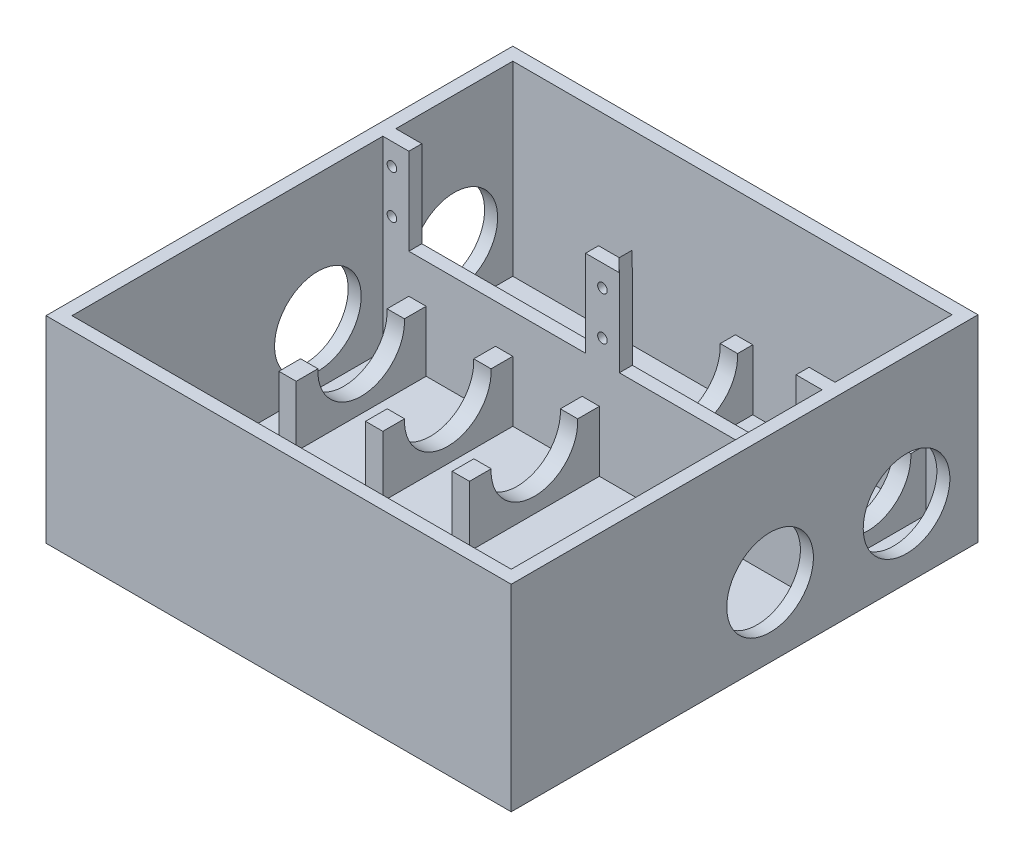
SolidWorks part; units mm, degrees
ref_plane "Front Plane" through (0, 0, 0) normal (0, 0, 1) x (1, 0, 0)
ref_plane "Top Plane" through (0, 0, 0) normal (0, 1, 0) x (1, 0, 0)
ref_plane "Right Plane" through (0, 0, 0) normal (1, 0, 0) x (0, 0, -1)
sketch "Sketch3" plane through (0, 0, 0) normal (0, 1, 0) x (1, 0, 0)
  line L1 (0, 0) -> (-107.4, 0)
  line L2 (0, 0) -> (0, -136.7612)
  line L3 (0, -136.7612) -> (-107.4, -136.7612)
  line L4 (-107.4, 0) -> (-107.4, -136.7612)
  dimension "D1" = 107.4
extrude "Boss-Extrude2" add sketch "Sketch3" along normal blind 2.5
sketch "Sketch4" plane through (0, 2.5, 0) normal (0, 1, 0) x (1, 0, 0)
  line L0 (-107.4, 0) -> (-107.4, -136.7612) construction
  line L1 (0, 0) -> (-107.4, 0) construction
  line L2 (-29, 0) -> (-29, -30)
  line L3 (-53, 0) -> (-49, 0)
  line L4 (-53, 0) -> (-53, -30)
  line L5 (-53, -30) -> (-49, -30)
  line L6 (-49, 0) -> (-49, -30)
  line L7 (-33, 0) -> (-33, -30)
  line L8 (-33, 0) -> (-29, 0)
  line L9 (-33, -30) -> (-29, -30)
  line L10 (-9, 0) -> (-9, -30)
  line L11 (-13, 0) -> (-13, -30)
  line L12 (-13, 0) -> (-9, 0)
  line L13 (-13, -30) -> (-9, -30)
  line L14 (-74.4, -33) -> (-74.4, -63)
  line L15 (-98.4, -33) -> (-94.4, -33)
  line L16 (-98.4, -33) -> (-98.4, -63)
  line L17 (-98.4, -63) -> (-94.4, -63)
  line L18 (-94.4, -33) -> (-94.4, -63)
  line L19 (-78.4, -33) -> (-78.4, -63)
  line L20 (-78.4, -33) -> (-74.4, -33)
  line L21 (-78.4, -63) -> (-74.4, -63)
  line L22 (-54.4, -33) -> (-54.4, -63)
  line L23 (-58.4, -33) -> (-58.4, -63)
  line L24 (-58.4, -33) -> (-54.4, -33)
  line L25 (-58.4, -63) -> (-54.4, -63)
  line L26 (0, -136.7612) -> (0, 0) construction
  point P0 (-100.4, -3)
  point P1 (-20.4, -3)
  point P7 (-100.4, -23)
  point P8 (-20.4, -23)
  dimension "D1" = 80
  dimension "D2" = 7
  dimension "D3" = 3
  dimension "D4" = 3
  dimension "D6" = 30
  dimension "D7" = 4
  dimension "D8" = 9
  dimension "D10" = 16
  dimension "D11" = 16
  dimension "D12" = 9
  dimension "D13" = 9
  dimension "D14" = 16
  dimension "D15" = 16
  dimension "D16" = 3
  dimension "D5" = 2
  dimension "D9" = 2
extrude "Boss-Extrude3" add sketch "Sketch4" along normal blind 14
sketch "Sketch7" plane through (0, 2.5, 0) normal (0, 1, 0) x (1, 0, 0)
  line L69 (-3, -3) -> (-9, -3)
  line L70 (-3, -133.7612) -> (-3, -3)
  line L71 (-104.4, -133.7612) -> (-3, -133.7612)
  line L72 (-53, -3) -> (-104.4, -3)
  line L73 (-104.4, -3) -> (-104.4, -133.7612)
  line L74 (-3, -3) -> (-9, -3)
  line L75 (-3, -133.7612) -> (-3, -3)
  line L76 (-104.4, -133.7612) -> (-3, -133.7612)
  line L77 (-53, -3) -> (-104.4, -3)
  line L78 (-104.4, -3) -> (-104.4, -133.7612)
  line L85 (-13, -3) -> (-29, -3)
  line L86 (-13, -3) -> (-29, -3)
  line L87 (-33, -3) -> (-33, 0)
  line L88 (-33, -3) -> (-49, -3)
  line L89 (-33, -3) -> (-49, -3)
  line L90 (-33, 0) -> (-49, 0)
  line L91 (-13, -3) -> (-13, 0)
  line L92 (-13, 0) -> (-29, 0)
  line L93 (-29, 0) -> (-29, -3)
  line L94 (-49, 0) -> (-49, -3)
  line L115 (-53, 0) -> (-107.4, 0)
  line L116 (-107.4, 0) -> (-107.4, -136.7612)
  line L117 (-107.4, -136.7612) -> (0, -136.7612)
  line L118 (0, 0) -> (-9, 0)
  line L119 (0, -136.7612) -> (0, 0)
  line L120 (-53, 0) -> (-107.4, 0)
  line L121 (-107.4, 0) -> (-107.4, -136.7612)
  line L122 (-107.4, -136.7612) -> (0, -136.7612)
  line L123 (0, 0) -> (-9, 0)
  line L124 (0, -136.7612) -> (0, 0)
  line M21 (-13, -30) -> (-13, 0)
  line M22 (-13, 0) -> (-29, 0)
  line M23 (-29, 0) -> (-29, -30)
  line M25 (-33, -30) -> (-33, 0)
  line M26 (-33, 0) -> (-49, 0)
  line M27 (-49, 0) -> (-49, -30)
  line M29 (-53, -30) -> (-53, 0)
  line M30 (-53, 0) -> (-107.4, 0)
  line M31 (-107.4, 0) -> (-107.4, -136.7612)
  line M32 (-107.4, -136.7612) -> (0, -136.7612)
  line M33 (0, -136.7612) -> (0, 0)
  line M34 (0, 0) -> (-9, 0)
  line M35 (-9, 0) -> (-9, -30)
  dimension "D1" = 3
  dimension "D2" = 3
  dimension "D3" = 3
  dimension "D5" = 0
extrude "Boss-Extrude5" add sketch "Sketch7" along normal blind 26 contours L89 M25 M26 M27 | L78 L77 L74 L75 L76 M29 M30 M31 M32 M33 M34 M35 | L86 M21 M22 M23 region at (-6, 2.5, 1.2611) region at (-21, 2.5, 1.5) region at (-41, 2.5, 1.5)
sketch "Sketch8" plane through (0, 2.5, 0) normal (0, 1, 0) x (1, 0, 0)
  line L0 (-104.4, -3) -> (-104.4, -133.7612) construction
  circle A0 centre (-72.4, -69) radius 1
  circle A1 centre (-26.68, -69) radius 1
  circle A2 centre (-26.68, -84.24) radius 1
  circle A3 centre (-72.4, -84.24) radius 1
  point P0 (-72.4, -69)
  point P2 (-26.68, -69)
  point P7 (-26.68, -84.24)
  point P8 (-72.4, -84.24)
  dimension "D4" = 2
  dimension "D1" = 32
  dimension "D2" = 6
  dimension "D5" = 2
  dimension "D3" = 2
  dimension "D6" = 2
extrude "Cut-Extrude3" cut sketch "Sketch8" against normal through all
sketch "Sketch10" plane through (0, 2.5, 0) normal (0, 1, 0) x (1, 0, 0)
  line L0 (-3, -133.7612) -> (-3, -3) construction
  line L1 (-3, -30) -> (-104.4, -30)
  line L2 (-3, -30) -> (-3, -33)
  line L3 (-3, -33) -> (-104.4, -33)
  line L4 (-104.4, -30) -> (-104.4, -33)
  line L5 (-104.4, -3) -> (-104.4, -133.7612) construction
  point P16 (-3, -77)
  point P19 (-104.4, -77)
  dimension "D1" = 3
  dimension "D2" = 0
extrude "Boss-Extrude6" add sketch "Sketch10" along normal blind 46
sketch "Sketch14" plane through (0, 0, 0) normal (0, -1, 0) x (1, 0, 0)
  line L1 (-107.4, 0) -> (-107.4, 136.7612) construction
  line L2 (0, 136.7612) -> (-107.4, 136.7612)
  line L3 (0, 136.7612) -> (0, 107.7612)
  line L4 (0, 107.7612) -> (-107.4, 107.7612)
  line L5 (-107.4, 136.7612) -> (-107.4, 107.7612)
  dimension "D1" = 29
extrude "Cut-Extrude7" cut sketch "Sketch14" against normal through all
sketch "Sketch15" plane through (0, 0, 33) normal (0, 0, 1) x (1, 0, 0)
  line L0 (-98.4, 48.5) -> (-98.4, 25.5)
  line L1 (-98.4, 25.5) -> (-57.6, 25.5)
  line L2 (-57.6, 48.5) -> (-57.6, 25.5)
  line L3 (-104.4, 48.5) -> (-3, 48.5) construction
  line L4 (-49.8234, 48.6106) -> (-49.8, 25.5)
  line L5 (-49.8, 25.5) -> (-9, 25.5)
  line L6 (-9, 48.5) -> (-9, 25.5)
  line L7 (-9, 48.5) -> (-49.8, 48.5)
  line L8 (-49.8, 48.5) -> (-49.8234, 48.6106)
  line L9 (-49.8, 48.5) -> (-49.8, 25.5) [skipped]
  circle A0 centre (-102.3, 30.5) radius 1.1036
  circle A3 centre (-102.3, 40.5) radius 1.1036
  circle A4 centre (-53.7, 30.5) radius 1.1036
  circle A5 centre (-53.7, 40.5) radius 1.1036
  circle A6 centre (-5.1, 40.5) radius 1.1036
  circle A7 centre (-5.1, 30.5) radius 1.1036
  point P6 (-78, 25.5)
  line M6 (-3, 48.5) -> (-104.4, 48.5)
  dimension "D13" = 0
  dimension "D1" = 24.3
  dimension "D4" = 0
  dimension "D5" = 6
  dimension "D6" = 8
  dimension "D7" = 40.8
  dimension "D9" = 23
  dimension "D11" = 10
  dimension "D14" = 2
extrude "Cut-Extrude11" cut sketch "Sketch15" against normal blind 14 contours L6 L4 L5 M6 | L2 L0 L1 M6 | A5 | A4 | A3 | A6 | A7 | A4 | A0 region at (-78, 37, 33) region at (-49.8078, 40.8333, 33) region at (-29.4, 37, 33) region at (-102.3, 40.5, 33) region at (-53.7, 30.5, 33) region at (-53.7, 40.5, 33) region at (-5.1, 40.5, 33) region at (-5.1, 30.5, 33)
sketch "Sketch17" plane through (-107.4, 0, 0) normal (-1, 0, 0) x (0, 0, 1)
  line L0 (0, 28.5) -> (0, 0) construction
  line L1 (0, 0) -> (107.7612, 0) construction
  circle A0 centre (16.5, 16) radius 10
  circle A1 centre (48, 16) radius 10
  point P0 (16.5, 16)
  point P3 (0, 14.25)
  point P8 (48, 16)
  dimension "D3" = 20
  dimension "D5" = 20
  dimension "D1" = 16.5
  dimension "D2" = 16
  dimension "D4" = 48
extrude "Cut-Extrude12" cut sketch "Sketch17" against normal through all
sketch "Sketch18" plane through (0, 2.5, 0) normal (0, 1, 0) x (1, 0, 0)
  line L0 (-104.4, -33) -> (-104.4, -107.7612) construction
  line L1 (-3, -107.7612) -> (-104.4, -107.7612)
  line L2 (-3, -107.7612) -> (-3, -104.7612)
  line L3 (-3, -104.7612) -> (-104.4, -104.7612)
  line L4 (-104.4, -107.7612) -> (-104.4, -104.7612)
  dimension "D1" = 3
extrude "Boss-Extrude7" add sketch "Sketch18" along normal blind 26
sketch "Sketch19" plane through (0, 16.5, 0) normal (0, 1, 0) x (1, 0, 0)
  line L0 (-33, -3) -> (-33, -6.5125) construction
  line L1 (-49, 0) -> (-53, 0)
  line L2 (-49, 0) -> (-49, -3)
  line L3 (-49, -3) -> (-53, -3)
  line L4 (-53, 0) -> (-53, -3)
  line L5 (-29, 0) -> (-33, 0)
  line L6 (-29, 0) -> (-29, -3)
  line L7 (-29, -3) -> (-33, -3)
  line L8 (-33, 0) -> (-33, -3)
  line L9 (-13, -3) -> (-13, -6.5125) construction
  line L10 (-9, 0) -> (-13, 0)
  line L11 (-9, 0) -> (-9, -3)
  line L12 (-9, -3) -> (-13, -3)
  line L13 (-13, 0) -> (-13, -3)
extrude "Boss-Extrude8" add sketch "Sketch19" along normal blind 12
sketch "Sketch20" plane through (0, 48.5, 0) normal (0, 1, 0) x (1, 0, 0)
  line L0 (-9, -33) -> (-3, -33) construction
  line L1 (-3, -30) -> (-9, -30)
  line L2 (-3, -30) -> (-3, -33)
  line L3 (-3, -33) -> (-9, -33)
  line L4 (-9, -30) -> (-9, -33)
  line L6 (-49.8233, -30) -> (-57.6, -30)
  line L7 (-49.8233, -30) -> (-49.8233, -33)
  line L8 (-49.8233, -33) -> (-57.6, -33)
  line L9 (-57.6, -30) -> (-57.6, -33)
  line L10 (-98.4, -30) -> (-104.4, -30)
  line L11 (-98.4, -30) -> (-98.4, -33)
  line L12 (-98.4, -33) -> (-104.4, -33)
  line L13 (-104.4, -30) -> (-104.4, -33)
extrude "Cut-Extrude13" cut sketch "Sketch20" against normal blind 3
sketch "Sketch21" plane through (0, 28.5, 0) normal (0, 1, 0) x (1, 0, 0)
  line L8 (0, -107.7612) -> (0, 0)
  line L9 (0, 0) -> (-107.4, 0)
  line L10 (-107.4, 0) -> (-107.4, -107.7612)
  line L11 (-107.4, -107.7612) -> (0, -107.7612)
  line L12 (0, -107.7612) -> (0, 0)
  line L13 (0, 0) -> (-107.4, 0)
  line L14 (-107.4, 0) -> (-107.4, -107.7612)
  line L15 (-107.4, -107.7612) -> (0, -107.7612)
  line L72 (-3, -3) -> (-104.4, -3)
  line L73 (-104.4, -3) -> (-104.4, -104.7612)
  line L74 (-104.4, -104.7612) -> (-3, -104.7612)
  line L75 (-3, -104.7612) -> (-3, -3)
  dimension "D1" = 0
extrude "Boss-Extrude9" add sketch "Sketch21" along normal blind 17
